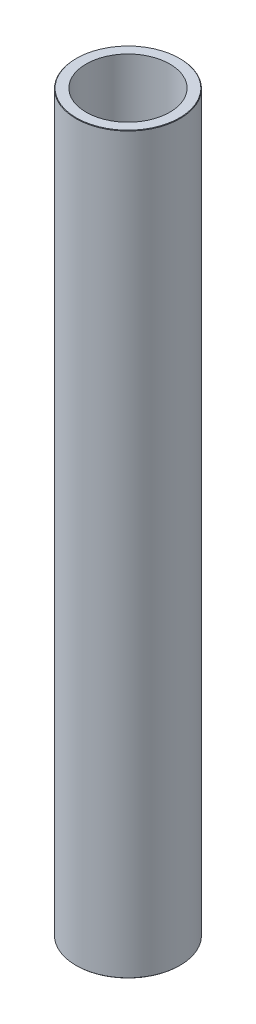
SolidWorks part; units mm, degrees
ref_plane "Front Plane" through (0, 0, 0) normal (0, 0, 1) x (1, 0, 0)
ref_plane "Top Plane" through (0, 0, 0) normal (0, 1, 0) x (1, 0, 0)
ref_plane "Right Plane" through (0, 0, 0) normal (1, 0, 0) x (0, 0, -1)
sketch "Sketch1" plane through (0, 0, 0) normal (0, 1, 0) x (1, 0, 0)
  circle A0 centre (0, 0) radius 42.5
  dimension "SHAFT_OD" = 85
extrude "Boss-Extrude1" add sketch "Sketch1" along normal blind 600
sketch "Sketch2" plane through (0, 0, 0) normal (0, 1, 0) x (1, 0, 0)
  circle A0 centre (0, 0) radius 34.1851
  dimension "BORE_D" = 68.3701
extrude "Cut-Extrude1" cut sketch "Sketch2" along normal through all
chamfer "Chamfer1" distance 0.365 angle 44.653 2 edges at (0, 600, 42.5) (0, 0, 42.5) first distance on face at (0, 600, 42.5) first distance on face at (0, 0, 34.1851)
